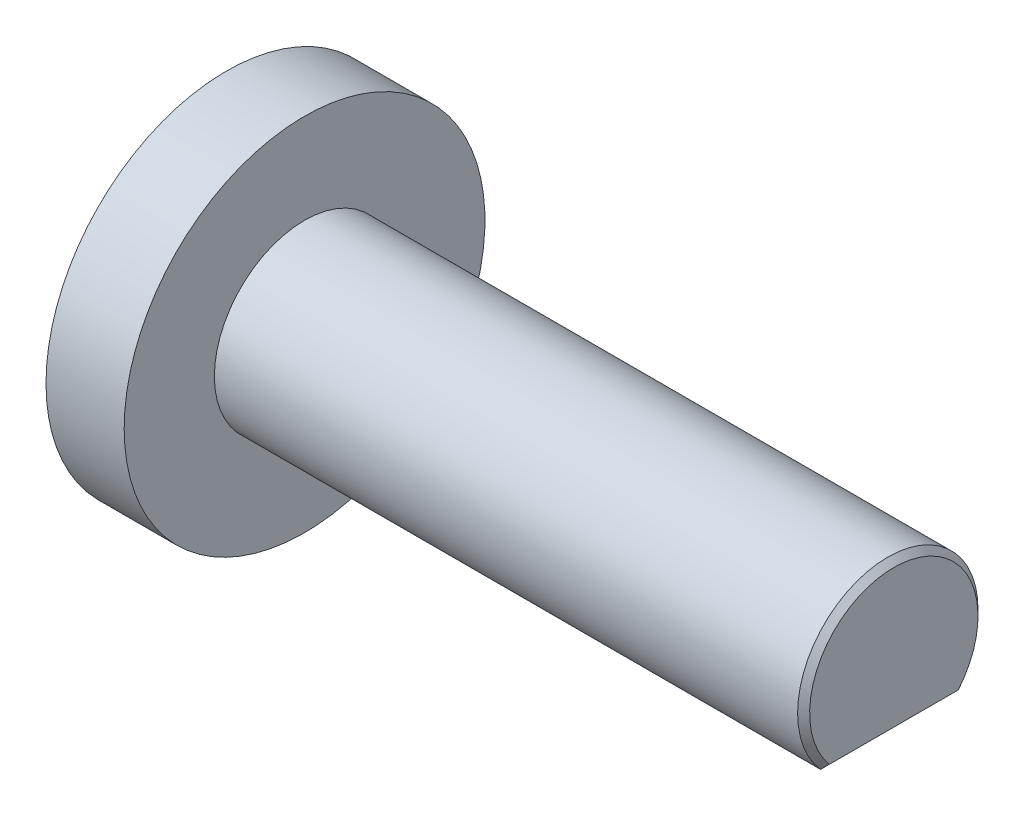
SolidWorks part; units mm, degrees
material "Unlegierter Baustahl"
ref_plane "Ebene vorne" through (0, 0, 0) normal (0, 0, 1) x (1, 0, 0)
ref_plane "Ebene oben" through (0, 0, 0) normal (0, 1, 0) x (1, 0, 0)
ref_plane "Ebene rechts" through (0, 0, 0) normal (1, 0, 0) x (0, 0, -1)
sketch "Skizze1" plane through (0, 0, 0) normal (0, 0, 1) x (1, 0, 0)
  line L0 (0, 0) -> (11.1, 0) construction
  line L1 (0, 0) -> (0, 3)
  line L2 (0, 3) -> (1.3, 3)
  line L3 (1.3, 3) -> (1.3, 1.5)
  line L4 (1.3, 1.5) -> (11.1, 1.5)
  line L5 (11.1, 1.5) -> (11.1, 0)
  line L6 (0, 0) -> (11.1, 0)
  dimension "D1" = 1.3
  dimension "D2" = 3
  dimension "D3" = 9.8
  dimension "D4" = 6
revolve "Rotation1" add sketch "Skizze1" angle 360 about L0
sketch "Skizze2" plane through (11.1, 0, 0) normal (1, 0, 0) x (0, 0, -1)
  line L1 (-1.118, -1) -> (1.118, -1)
  line L2 (-1.118, -1) -> (-1.118, -1.5)
  line L3 (-1.118, -1.5) -> (1.118, -1.5)
  line L4 (1.118, -1) -> (1.118, -1.5)
  circle A0 centre (0, 0) radius 1.5 construction
  dimension "D1" = 1
extrude "Schnitt-Linear austragen1" cut sketch "Skizze2" against normal blind 9
chamfer "Fase1" distance 0.1 angle 45 2 edges at (11.1, 1.5, 0) (11.1, -1, 0)
